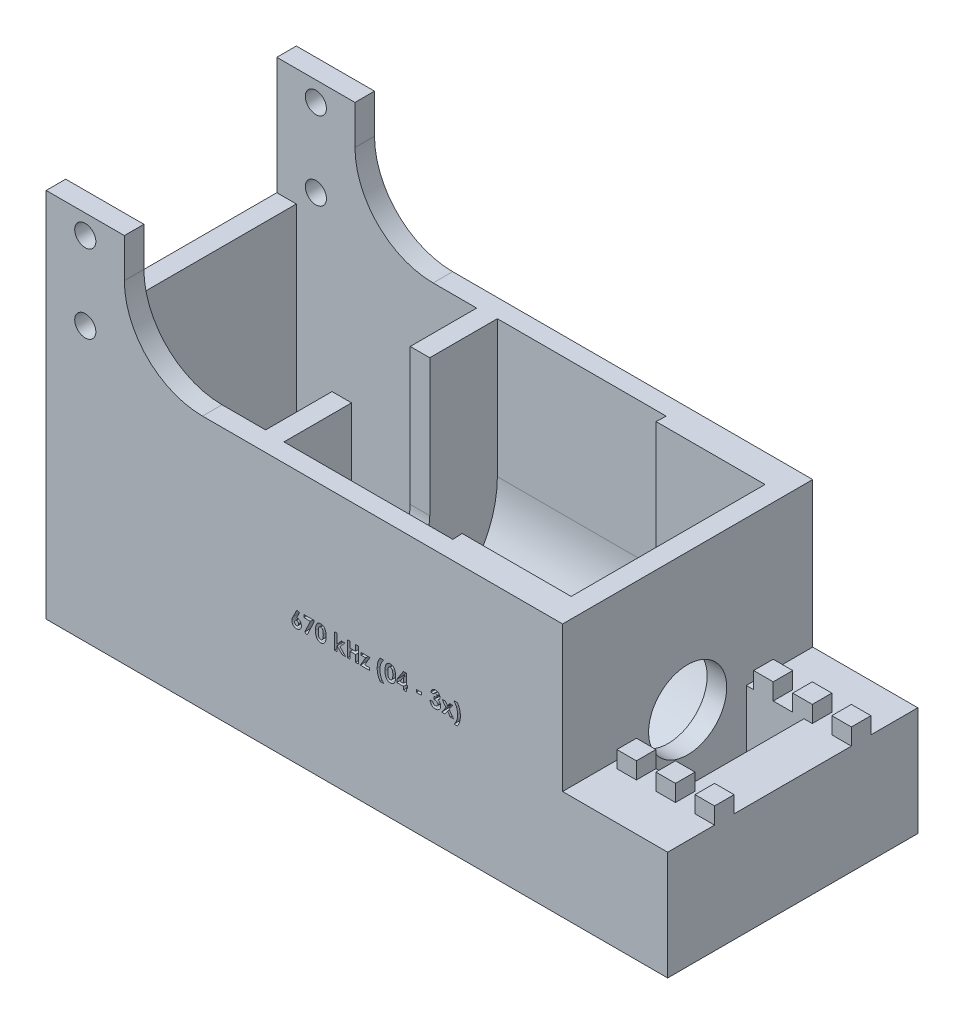
SolidWorks part; units mm, degrees
ref_plane "Front Plane" through (0, 0, 0) normal (0, 0, 1) x (1, 0, 0)
ref_plane "Top Plane" through (0, 0, 0) normal (0, 1, 0) x (1, 0, 0)
ref_plane "Right Plane" through (0, 0, 0) normal (1, 0, 0) x (0, 0, -1)
sketch "Sketch1" plane through (0, 0, 0) normal (0, 0, 1) x (1, 0, 0)
  line L1 (-76.2, -76.2) -> (81.28, -76.2)
  line L2 (-76.2, -76.2) -> (-76.2, 0)
  line L3 (-76.2, 0) -> (81.28, 0)
  line L4 (81.28, -76.2) -> (81.28, 0)
  line L5 (-76.2, -76.2) -> (81.28, 0) construction
  line L6 (-76.2, 0) -> (81.28, -76.2) construction
  point P0 (0, 0)
  dimension "D1" = 157.48
  dimension "D2" = 76.2
  dimension "D3" = 76.2
extrude "Boss-Extrude1" add sketch "Sketch1" along normal mid plane 81.28
sketch "Sketch2" plane through (0, 0, 0) normal (0, 0, 1) x (1, 0, 0)
  line L1 (-49.3609, -3.429) -> (-49.3609, -25.4)
  line L3 (81.28, 0) -> (-76.2, 0) construction
  line L4 (5.5031, -3.429) -> (5.3613, -6.6008)
  line L5 (3.9535, -38.1) -> (5.5031, -3.429) construction
  line L6 (-76.2, -38.1) -> (19.6294, -38.1)
  line L7 (19.6294, -38.1) -> (72.5335, -38.1)
  line L8 (-607.3619, -38.1) -> (19.6294, -38.1) construction
  line L9 (-49.3609, -3.429) -> (5.5031, -3.429)
  line L11 (5.3613, -6.6008) -> (47.1335, -6.6008)
  line L12 (47.1335, -6.6008) -> (47.1335, -28.194)
  line L13 (47.1335, -28.194) -> (72.5335, -28.194)
  line L14 (-49.3609, -25.4) -> (-76.2, -25.4)
  line L15 (-76.2, -25.4) -> (-76.2, -38.1)
  line L16 (81.28, 0) -> (-76.2, 0) construction
  line L17 (-76.2, 0) -> (-76.2, -76.2) construction
  line L20 (72.5335, -28.194) -> (72.5335, -38.1)
  line L21 (-76.2, 0) -> (-76.2, -76.2) construction
  point P23 (3.9535, -38.1)
  dimension "D1" = 38.1
  dimension "D2" = 54.864
  dimension "D3" = 34.671
  dimension "D4" = 68.58
  dimension "D5" = 9.906
  dimension "D6" = 3.175
  dimension "D7" = 26.8391
  dimension "D8" = 25.4
  dimension "D9" = 12.7
revolve "Cut-Revolve1" cut sketch "Sketch2" angle 360 about L8
sketch "Sketch37" plane through (81.28, 0, 0) normal (1, 0, 0) x (0, 0, -1)
  line L0 (40.64, -76.2) -> (40.64, 0) construction
  line L1 (-40.64, 0) -> (40.64, 0)
  line L2 (-40.64, 0) -> (-40.64, -38.1)
  line L3 (-40.64, -38.1) -> (40.64, -38.1)
  line L4 (40.64, 0) -> (40.64, -38.1)
  point P7 (0, -38.1)
  point P11 (0, 0)
  dimension "D1" = 38.1
extrude "Cut-Extrude32" cut sketch "Sketch37" against normal through all
sketch "Sketch39" plane through (0, -38.1, 0) normal (0, 1, 0) x (1, 0, 0)
  line L20 (-49.3609, -12.7) -> (-76.2, -12.7)
  line L21 (-49.3609, -12.7) -> (-76.2, -12.7)
  line L22 (-76.2, 40.64) -> (-76.2, 12.7)
  line L23 (-76.2, 40.64) -> (-76.2, 12.7)
  line L24 (-76.2, 12.7) -> (-49.3609, 12.7)
  line L25 (-76.2, -12.7) -> (-76.2, -40.64)
  line L26 (-76.2, -40.64) -> (81.28, -40.64)
  line L27 (81.28, -40.64) -> (81.28, 40.64)
  line L28 (81.28, 40.64) -> (-76.2, 40.64)
  line L29 (-76.2, 12.7) -> (-49.3609, 12.7)
  line L30 (-49.3609, 12.7) -> (-49.3609, 34.671)
  line L31 (-49.3609, 12.7) -> (-49.3609, 34.671)
  line L32 (-49.3609, 34.671) -> (5.5031, 34.671)
  line L33 (-49.3609, 34.671) -> (5.5031, 34.671)
  line L34 (5.5031, 34.671) -> (5.3613, 31.4992)
  line L35 (5.5031, 34.671) -> (5.3613, 31.4992)
  line L36 (5.3613, 31.4992) -> (47.1335, 31.4992)
  line L37 (5.3613, 31.4992) -> (47.1335, 31.4992)
  line L38 (47.1335, 31.4992) -> (47.1335, 9.906)
  line L39 (47.1335, 31.4992) -> (47.1335, 9.906)
  line L40 (47.1335, 9.906) -> (72.5335, 9.906)
  line L41 (47.1335, 9.906) -> (72.5335, 9.906)
  line L42 (72.5335, 9.906) -> (72.5335, -9.906)
  line L43 (72.5335, 9.906) -> (72.5335, -9.906)
  line L44 (72.5335, -9.906) -> (47.1335, -9.906)
  line L45 (72.5335, -9.906) -> (47.1335, -9.906)
  line L46 (47.1335, -9.906) -> (47.1335, -31.4992)
  line L47 (47.1335, -9.906) -> (47.1335, -31.4992)
  line L48 (47.1335, -31.4992) -> (5.3613, -31.4992)
  line L49 (-76.2, -12.7) -> (-76.2, -40.64)
  line L50 (-76.2, -40.64) -> (81.28, -40.64)
  line L51 (81.28, -40.64) -> (81.28, 40.64)
  line L52 (81.28, 40.64) -> (-76.2, 40.64)
  line L53 (47.1335, -31.4992) -> (5.3613, -31.4992)
  line L54 (5.3613, -31.4992) -> (5.5031, -34.671)
  line L55 (5.3613, -31.4992) -> (5.5031, -34.671)
  line L56 (5.5031, -34.671) -> (-49.3609, -34.671)
  line L57 (5.5031, -34.671) -> (-49.3609, -34.671)
  line L58 (-49.3609, -34.671) -> (-49.3609, -12.7)
  line L59 (-49.3609, -34.671) -> (-49.3609, -12.7)
  dimension "D1" = 0
extrude "Boss-Extrude5" add sketch "Sketch39" along normal blind 44.45
ref_axis "Axis1" through (72.5335, -38.1, 0) along (-1, 0, 0)
ref_plane "Plane_Mid" through (0, -38.1, 0) normal (0, 1, 0) x (1, 0, 0)
ref_plane "Plane3" through (0, -40.7987, 0) normal (0, 1, 0) x (1, 0, 0)
sketch "Sketch45" plane through (0, 0, 0) normal (0, 0, 1) x (1, 0, 0)
  line L1 (27.94, -40.7987) -> (-27.94, -40.7988) construction
  line L2 (81.28, 6.35) -> (47.1335, 6.35)
  line L4 (81.28, 6.35) -> (81.28, -40.7987)
  line L5 (81.28, -40.7987) -> (47.1335, -40.7987)
  line L8 (47.1335, 6.35) -> (47.1335, -40.7987)
extrude "Cut-Extrude54" cut sketch "Sketch45" against normal through all both and the other way through all
ref_plane "Plane1" through (-74.7609, 0, 0) normal (1, 0, 0) x (0, 0, -1)
sketch "Sketch97" plane through (0, 6.35, 0) normal (0, 1, 0) x (1, 0, 0)
  line L0 (-76.2, -40.64) -> (47.1335, -40.64) construction
  line L1 (-76.2, 40.64) -> (-55.7109, 40.64)
  line L2 (-76.2, 40.64) -> (-76.2, -40.64)
  line L3 (-76.2, -40.64) -> (-55.7109, -40.64)
  line L4 (-55.7109, 40.64) -> (-55.7109, -40.64)
  line L5 (-49.3609, 12.7) -> (-49.3609, 34.671) construction
  dimension "D1" = 6.35
extrude "Cut-Extrude72" cut sketch "Sketch97" against normal offset from surface (76.2 mm away) 6.35 up to face at (2.54, -76.2, 0)
ref_plane "Plane2" through (0, -38.1, 0) normal (0, 1, 0) x (1, 0, 0)
ref_point "Point1"
sketch "Sketch99" plane through (0, 6.35, 0) normal (0, 1, 0) x (1, 0, 0)
  line L8 (81.28, 40.64) -> (81.28, -40.64) construction
  line L9 (47.1335, 19.05) -> (74.93, 19.05)
  line L10 (47.1335, 19.05) -> (47.1335, -19.05)
  line L11 (47.1335, -19.05) -> (74.93, -19.05)
  line L12 (74.93, 19.05) -> (74.93, -19.05)
  line L15 (47.1335, 40.64) -> (47.1335, 31.4992) construction
  point P7 (74.93, 0)
  dimension "D1" = 6.35
  dimension "D2" = 38.1
extrude "Cut-Extrude74" cut sketch "Sketch99" against normal through all
sketch "Sketch101" plane through (0, -40.7987, 0) normal (0, 1, 0) x (1, 0, 0)
  line L0 (49.53, 25.4) -> (55.88, 25.4)
  line L1 (49.53, 25.4) -> (49.53, 19.05)
  line L2 (49.53, 19.05) -> (55.88, 19.05)
  line L3 (55.88, 25.4) -> (55.88, 19.05)
  line L4 (62.23, 25.4) -> (68.58, 25.4)
  line L5 (62.23, 25.4) -> (62.23, 19.05)
  line L6 (62.23, 19.05) -> (68.58, 19.05)
  line L7 (68.58, 25.4) -> (68.58, 19.05)
  line L8 (74.93, 25.4) -> (81.28, 25.4)
  line L9 (74.93, 25.4) -> (74.93, 19.05)
  line L10 (74.93, 19.05) -> (81.28, 19.05)
  line L11 (81.28, 25.4) -> (81.28, 19.05)
  line L13 (81.28, 0) -> (0, 0) construction
  line L14 (81.28, 40.64) -> (81.28, -40.64) construction
  line L15 (81.28, -25.4) -> (81.28, -19.05)
  line L16 (74.93, -19.05) -> (81.28, -19.05)
  line L17 (74.93, -25.4) -> (74.93, -19.05)
  line L18 (74.93, -25.4) -> (81.28, -25.4)
  line L19 (68.58, -25.4) -> (68.58, -19.05)
  line L20 (62.23, -19.05) -> (68.58, -19.05)
  line L21 (62.23, -25.4) -> (62.23, -19.05)
  line L22 (62.23, -25.4) -> (68.58, -25.4)
  line L23 (55.88, -25.4) -> (55.88, -19.05)
  line L24 (49.53, -19.05) -> (55.88, -19.05)
  line L25 (49.53, -25.4) -> (49.53, -19.05)
  line L26 (49.53, -25.4) -> (55.88, -25.4)
  point P31 (74.93, 22.225)
  dimension "D1" = 6.35
  dimension "D2" = 6.35
  dimension "D3" = 6.35
extrude "Boss-Extrude7" add sketch "Sketch101" along normal blind 5.3975
sketch "Sketch102" plane through (0, 6.35, 0) normal (0, 1, 0) x (1, 0, 0)
  line L0 (-76.2, -40.64) -> (-76.2, 40.64) construction
  line L1 (-55.7109, 40.64) -> (-76.2, 40.64)
  line L2 (-55.7109, 40.64) -> (-55.7109, 34.29)
  line L3 (-55.7109, 34.29) -> (-76.2, 34.29)
  line L4 (-76.2, 40.64) -> (-76.2, 34.29)
  line L5 (-55.7109, -40.64) -> (-76.2, -40.64)
  line L6 (-55.7109, -40.64) -> (-55.7109, -34.29)
  line L7 (-55.7109, -34.29) -> (-76.2, -34.29)
  line L8 (-76.2, -40.64) -> (-76.2, -34.29)
  dimension "D1" = 6.35
extrude "Boss-Extrude8" add sketch "Sketch102" against normal up to next
sketch "Sketch104" plane through (0, 0, 40.64) normal (0, 0, 1) x (1, 0, 0)
  line L0 (-76.2, 6.35) -> (-76.2, -76.2) construction
  line L1 (-76.2, -38.1) -> (47.1335, -38.1) construction
  text T0 "<b>670 kHz (04 - 3x)</b>" font "Century Gothic" height 5.08
extrude "Cut-Extrude76" cut sketch "Sketch104" against normal blind 2.54
sketch "Sketch105" plane through (0, 6.35, 0) normal (0, 1, 0) x (1, 0, 0)
  line L0 (-76.2, -40.64) -> (47.1335, -40.64) construction
  line L1 (47.1335, 40.64) -> (40.7835, 40.64)
  line L2 (47.1335, 40.64) -> (47.1335, -40.64)
  line L3 (47.1335, -40.64) -> (40.7835, -40.64)
  line L4 (40.7835, 40.64) -> (40.7835, -40.64)
  dimension "D1" = 6.35
extrude "Boss-Extrude9" add sketch "Sketch105" against normal up to next
sketch "Sketch106" plane through (40.7835, 0, 0) normal (-1, 0, 0) x (0, 0, 1)
  circle A0 centre (0, -38.1) radius 12.7
  dimension "D1" = 25.4
extrude "Cut-Extrude77" cut sketch "Sketch106" against normal up to next
sketch "Sketch107" plane through (-76.2, 0, 0) normal (-1, 0, 0) x (0, 0, 1)
  line L8 (40.64, -76.2) -> (40.64, 6.35)
  line L9 (40.64, 6.35) -> (34.29, 6.35)
  line L10 (34.29, 6.35) -> (34.29, -69.85)
  line L11 (34.29, -69.85) -> (-34.29, -69.85)
  line L12 (-34.29, -69.85) -> (-34.29, 6.35)
  line L13 (-34.29, 6.35) -> (-40.64, 6.35)
  line L14 (-40.64, 6.35) -> (-40.64, -76.2)
  line L15 (-40.64, -76.2) -> (40.64, -76.2)
  line L16 (40.64, -76.2) -> (40.64, 6.35)
  line L17 (40.64, 6.35) -> (34.29, 6.35)
  line L18 (34.29, 6.35) -> (34.29, -69.85)
  line L19 (34.29, -69.85) -> (-34.29, -69.85)
  line L20 (-34.29, -69.85) -> (-34.29, 6.35)
  line L21 (-34.29, 6.35) -> (-40.64, 6.35)
  line L22 (-40.64, 6.35) -> (-40.64, -76.2)
  line L23 (-40.64, -76.2) -> (40.64, -76.2)
  dimension "D1" = 0
extrude "Boss-Extrude10" add sketch "Sketch107" along normal blind 38.1
sketch "Sketch108" plane through (-114.3, 0, 0) normal (-1, 0, 0) x (0, 0, 1)
  line L1 (-40.64, -76.2) -> (40.64, -76.2)
  line L2 (-40.64, -76.2) -> (-40.64, 6.35)
  line L3 (-40.64, 6.35) -> (40.64, 6.35)
  line L4 (40.64, -76.2) -> (40.64, 6.35)
extrude "Boss-Extrude11" add sketch "Sketch108" along normal blind 6.35
sketch "Sketch109" plane through (0, -40.7987, 0) normal (0, 1, 0) x (1, 0, 0)
  line L1 (74.93, 19.05) -> (65.88, 19.05)
  line L2 (74.93, 19.05) -> (74.93, -19.05)
  line L3 (74.93, -19.05) -> (65.88, -19.05)
  line L4 (65.88, 19.05) -> (65.88, -19.05)
  line L6 (81.28, 19.05) -> (81.28, -19.05) construction
  dimension "D1" = 15.4
extrude "Boss-Extrude12" add sketch "Sketch109" against normal up to surface (35.4012 mm away) up to face at (61.0317, -76.2, 0)
sketch "Sketch110" plane through (0, 0, 40.64) normal (0, 0, 1) x (1, 0, 0)
  line L1 (-120.65, 6.35) -> (-95.25, 6.35)
  line L2 (-120.65, 6.35) -> (-120.65, 44.45)
  line L3 (-120.65, 44.45) -> (-95.25, 44.45)
  line L4 (-95.25, 6.35) -> (-95.25, 44.45)
  circle A0 centre (-107.95, 38.1) radius 3.429
  circle A1 centre (-107.95, 12.7) radius 3.429
  point P8 (-107.95, 44.45)
  dimension "D3" = 6.858
  dimension "D1" = 25.4
  dimension "D2" = 38.1
  dimension "D4" = 6.35
  dimension "D5" = 2
extrude "Boss-Extrude13" add sketch "Sketch110" against normal blind 6.35
mirror "Mirror1" about plane through (0, 0, 0) normal (0, 0, 1) of "Boss-Extrude13"
fillet "Fillet1" radius 25.4 2 edges at (-95.25, 6.35, 37.465) (-95.25, 6.35, -37.465)
